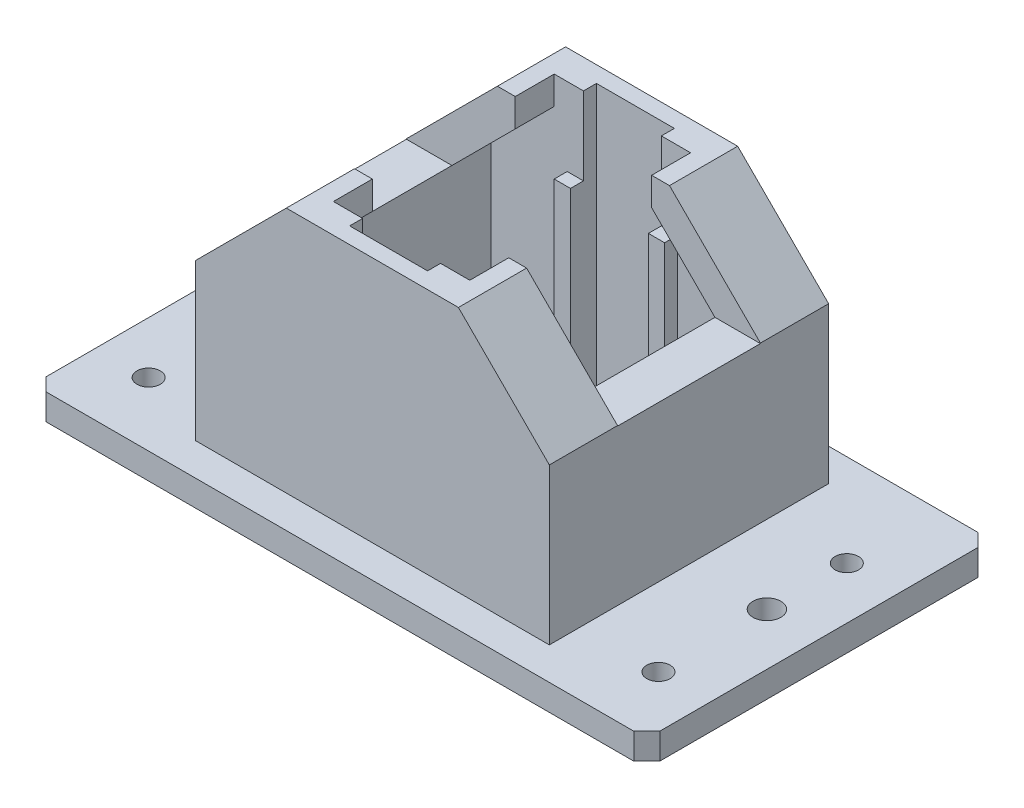
SolidWorks part; units mm, degrees
ref_plane "Płaszczyzna przednia" through (0, 0, 0) normal (0, 0, 1) x (1, 0, 0)
ref_plane "Płaszczyzna górna" through (0, 0, 0) normal (0, 1, 0) x (1, 0, 0)
ref_plane "Płaszczyzna prawa" through (0, 0, 0) normal (1, 0, 0) x (0, 0, -1)
sketch "Sketch1" plane through (0, 0, 0) normal (0, 1, 0) x (1, 0, 0)
  line L0 (0, 19.4294) -> (0, -20.6549) construction
  line L1 (-20.25, 17) -> (20.25, 17)
  line L2 (-20.25, 17) -> (-20.25, -17)
  line L3 (-20.25, -17) -> (20.25, -17)
  line L4 (20.25, 17) -> (20.25, -17)
  line L5 (-20.25, 17) -> (20.25, -17) construction
  line L6 (-20.25, -17) -> (20.25, 17) construction
  line L7 (-32.8665, 0) -> (32.8665, 0) construction
  line L8 (8.5, 15) -> (6, 15)
  line L9 (-8.5, 17) -> (-6, 17)
  line L10 (-8.5, 17) -> (-8.5, 15)
  line L11 (-8.5, 15) -> (-6, 15)
  line L12 (-6, 17) -> (-6, 15)
  line L13 (6, 17) -> (6, 15)
  line L14 (8.5, 17) -> (6, 17)
  line L15 (8.5, 17) -> (8.5, 15)
  line L16 (8.5, -17) -> (8.5, -15)
  line L17 (8.5, -17) -> (6, -17)
  line L18 (6, -17) -> (6, -15)
  line L19 (8.5, -15) -> (6, -15)
  line L20 (-8.5, -15) -> (-6, -15)
  line L21 (-6, -17) -> (-6, -15)
  line L22 (-8.5, -17) -> (-6, -17)
  line L23 (-8.5, -17) -> (-8.5, -15)
  line L24 (-27.25, 24) -> (-27.25, -24)
  line L25 (-27.25, -24) -> (27.25, -24)
  line L26 (27.25, 24) -> (27.25, -24)
  line L27 (-27.25, 24) -> (27.25, 24)
  point P0 (0, 0)
  point P10 (0, 17)
  dimension "D1" = 34
  dimension "D2" = 40.5
  dimension "D3" = 2.5
  dimension "D4" = 2
  dimension "D5" = 6
  dimension "1" = 7
extrude "Boss-Extrude1" add sketch "Sketch1" along normal blind 42 contours L15 L1 L13 L8 | L27 L24 L25 L26 L22 L23 L3 L2 L1 L4 L21 | L11 L12 L9 L10 | L20 L21 L22 L23 | L19 L18 L17 L16 region at (7.25, 0, -16) region at (0, 0, -23.2738)
chamfer "Chamfer2" distance 14 angle 45 2 edges at (27.25, 42, 0) (-27.25, 42, 0)
chamfer "Chamfer3" distance 10 angle 45 2 edges at (20.25, 35, 0) (-20.25, 35, 0) first distance on face at (18.5, 36.75, 0) first distance on face at (-18.5, 36.75, 0)
sketch "Sketch2" plane through (0, 0, -17) normal (0, 0, 1) x (1, 0, 0)
  line L1 (-27.25, 20.9289) -> (-6.1789, 42)
  line L3 (-27.25, 28) -> (-27.25, 27.9289) construction
  line L8 (0, 51.2829) -> (0, -13.1032) construction
  line L9 (-6, 42) -> (6, 42) construction
  line L12 (-27.25, 28) -> (-13.25, 42)
  line L13 (-13.25, 42) -> (-6.1789, 42)
  line L14 (-13.25, 42) -> (-27.25, 28) construction
  line L15 (-27.25, 28) -> (-27.25, 20.9289)
  line L16 (13.25, 42) -> (6.1789, 42)
  line L17 (27.25, 28) -> (13.25, 42)
  line L18 (27.25, 28) -> (27.25, 20.9289)
  line L19 (27.25, 20.9289) -> (6.1789, 42)
  dimension "D1" = 5
extrude "Boss-Extrude2" add sketch "Sketch2" along normal blind 6
ref_plane "Plane1" through (0, 0, 0) normal (0, 0, 1) x (1, 0, 0)
mirror "Mirror2" about plane through (0, 0, 0) normal (0, 0, 1) of "Boss-Extrude2"
sketch "Sketch4" plane through (0, 0, 0) normal (0, -1, 0) x (1, 0, 0)
  line L0 (0, 30.4744) -> (0, -31.4814) construction
  line L1 (27.25, 24) -> (47.25, 24)
  line L2 (27.25, 24) -> (27.25, -24)
  line L3 (27.25, -24) -> (47.25, -24)
  line L4 (47.25, 24) -> (47.25, -24)
  line L5 (-27.25, -24) -> (-47.25, -24)
  line L6 (-47.25, 24) -> (-47.25, -24)
  line L7 (-27.25, 24) -> (-47.25, 24)
  line L8 (-27.25, 24) -> (-27.25, -24)
  line L9 (-55.8577, 0) -> (55.4548, 0) construction
  dimension "D1" = 20
extrude "Boss-Extrude3" add sketch "Sketch4" against normal blind 4
sketch "Sketch5" plane through (0, 42, 0) normal (0, 1, 0) x (1, 0, 0)
  line L0 (0, 26.9268) -> (0, -17) construction
  line L1 (-10.5, 17) -> (10.5, 17)
  line L2 (-10.5, 17) -> (-10.5, -17)
  line L3 (-10.5, -17) -> (10.5, -17)
  line L4 (10.5, 17) -> (10.5, -17)
  line L7 (20.25, -17) -> (8.5, -17) construction
  line L8 (-6, 17) -> (6, 17) construction
  dimension "D1" = 21
extrude "Cut-Extrude1" cut sketch "Sketch5" against normal blind 12
sketch "Sketch6" plane through (0, 0, 17) normal (0, 0, -1) x (-1, 0, 0)
  line L0 (10.5, 42) -> (-10.5, 42) construction
  line L1 (-6, 42) -> (6, 42)
  line L2 (-6, 42) -> (-6, 0)
  line L3 (-6, 0) -> (6, 0)
  line L4 (6, 42) -> (6, 0)
extrude "Cut-Extrude2" cut sketch "Sketch6" against normal blind 2
mirror "Mirror3" about plane through (0, 0, 0) normal (0, 0, 1) of "Cut-Extrude2"
sketch "Sketch7" plane through (0, 0, -24) normal (0, 0, -1) x (-1, 0, 0)
  line L10 (13.25, 42) -> (-13.25, 42)
  line L11 (-13.25, 42) -> (-27.25, 28)
  line L12 (-27.25, 28) -> (-27.25, 4)
  line L13 (-27.25, 4) -> (-47.25, 4)
  line L14 (-47.25, 4) -> (-47.25, 0)
  line L15 (-47.25, 0) -> (47.25, 0)
  line L16 (47.25, 0) -> (47.25, 4)
  line L17 (47.25, 4) -> (27.25, 4)
  line L18 (27.25, 4) -> (27.25, 28)
  line L19 (27.25, 28) -> (13.25, 42)
  line L20 (13.25, 42) -> (-13.25, 42)
  line L21 (-13.25, 42) -> (-27.25, 28)
  line L22 (-27.25, 28) -> (-27.25, 4)
  line L23 (-27.25, 4) -> (-47.25, 4)
  line L24 (-47.25, 4) -> (-47.25, 0)
  line L25 (-47.25, 0) -> (47.25, 0)
  line L26 (47.25, 0) -> (47.25, 4)
  line L27 (47.25, 4) -> (27.25, 4)
  line L28 (27.25, 4) -> (27.25, 28)
  line L29 (27.25, 28) -> (13.25, 42)
  dimension "D1" = 0
extrude "Cut-Extrude3" cut sketch "Sketch7" against normal blind 2.5
sketch "Sketch8" plane through (0, 0, 24) normal (0, 0, 1) x (1, 0, 0)
  line L10 (27.25, 4) -> (27.25, 28)
  line L11 (27.25, 28) -> (13.25, 42)
  line L12 (13.25, 42) -> (-13.25, 42)
  line L13 (-13.25, 42) -> (-27.25, 28)
  line L14 (-27.25, 28) -> (-27.25, 4)
  line L15 (-27.25, 4) -> (-47.25, 4)
  line L16 (-47.25, 4) -> (-47.25, 0)
  line L17 (-47.25, 0) -> (47.25, 0)
  line L18 (47.25, 0) -> (47.25, 4)
  line L19 (47.25, 4) -> (27.25, 4)
  line L20 (27.25, 4) -> (27.25, 28)
  line L21 (27.25, 28) -> (13.25, 42)
  line L22 (13.25, 42) -> (-13.25, 42)
  line L23 (-13.25, 42) -> (-27.25, 28)
  line L24 (-27.25, 28) -> (-27.25, 4)
  line L25 (-27.25, 4) -> (-47.25, 4)
  line L26 (-47.25, 4) -> (-47.25, 0)
  line L27 (-47.25, 0) -> (47.25, 0)
  line L28 (47.25, 0) -> (47.25, 4)
  line L29 (47.25, 4) -> (27.25, 4)
  dimension "D1" = 0
extrude "Cut-Extrude4" cut sketch "Sketch8" against normal blind 2.5
sketch "Sketch11" plane through (0, 0, 0) normal (0, -1, 0) x (-1, 0, 0)
  point P0 (-39.25, 12.3)
  point P3 (-39.25, -16.7)
  point P6 (39.25, 12.3)
  point P9 (39.25, -16.7)
hole_wizard "M3 Clearance Hole1" positions "Sketch11" profile "Sketch10" hole size "M3" standard "DIN"
sketch "Sketch10" plane through (39.25, 0, -12.3) normal (1, 0, 0) x (0, 0, -1)
  line L0 (0, 0) -> (0, 11.0815)
  line L1 (0, 11.0815) -> (1.8, 10)
  line L2 (1.8, 10) -> (1.8, 0)
  line L5 (1.8, 0) -> (0, 0)
  line L10 (0, 11.0815) -> (-1.8, 10) construction
  line L11 (0, -6.35) -> (0, 107.95) construction
  dimension "Hole Dia." = 3.6
  dimension "Hole Depth" = 10
  dimension "Drill Angle" = 118
sketch "Sketch12" plane through (0, 0, 0) normal (0, -1, 0) x (1, 0, 0)
  line L1 (-47.25, 21.5) -> (47.25, 21.5)
  line L2 (-47.25, 21.5) -> (-47.25, 26.5)
  line L3 (-47.25, 26.5) -> (47.25, 26.5)
  line L4 (47.25, 21.5) -> (47.25, 26.5)
  line L5 (47.25, -21.5) -> (-47.25, -21.5)
  line L6 (47.25, -21.5) -> (47.25, -26.5)
  line L7 (47.25, -26.5) -> (-47.25, -26.5)
  line L8 (-47.25, -21.5) -> (-47.25, -26.5)
  dimension "D1" = 5
extrude "Boss-Extrude4" add sketch "Sketch12" against normal up to surface (4 mm away) up to face at (-39.25, 4, -10.5)
chamfer "Chamfer4" distance 2 angle 45 4 edges at (-47.25, 2, -26.5) (47.25, 2, -26.5) (47.25, 2, 26.5) (-47.25, 2, 26.5)
sketch "Sketch15" plane through (0, 4, 0) normal (0, 1, 0) x (1, 0, 0)
  line L0 (-47.25, 0) -> (47.25, 0) construction
  line L1 (-47.25, -24.5) -> (-47.25, 24.5) construction
  line L2 (47.25, 24.5) -> (47.25, -24.5) construction
  point P8 (-39.25, 0)
  point P10 (39.25, 0)
  dimension "D1" = 8
  dimension "D2" = 8
hole_wizard "Ø4.3 (4.3) Diameter Hole1" positions "Sketch15" profile "Sketch14" hole size "Ø4.3" standard "DIN" end condition through all
sketch "Sketch14" plane through (39.25, 4, 0) normal (1, 0, 0) x (0, 0, 1)
  line L0 (0, 0) -> (0, 4)
  line L1 (0, 4) -> (2.15, 4)
  line L2 (2.15, 4) -> (2.15, 0)
  line L5 (2.15, 0) -> (0, 0)
  line L11 (0, -6.35) -> (0, 107.95) construction
  dimension "Thru Hole Dia." = 4.3
  dimension "Thru Hole Depth" = 4
